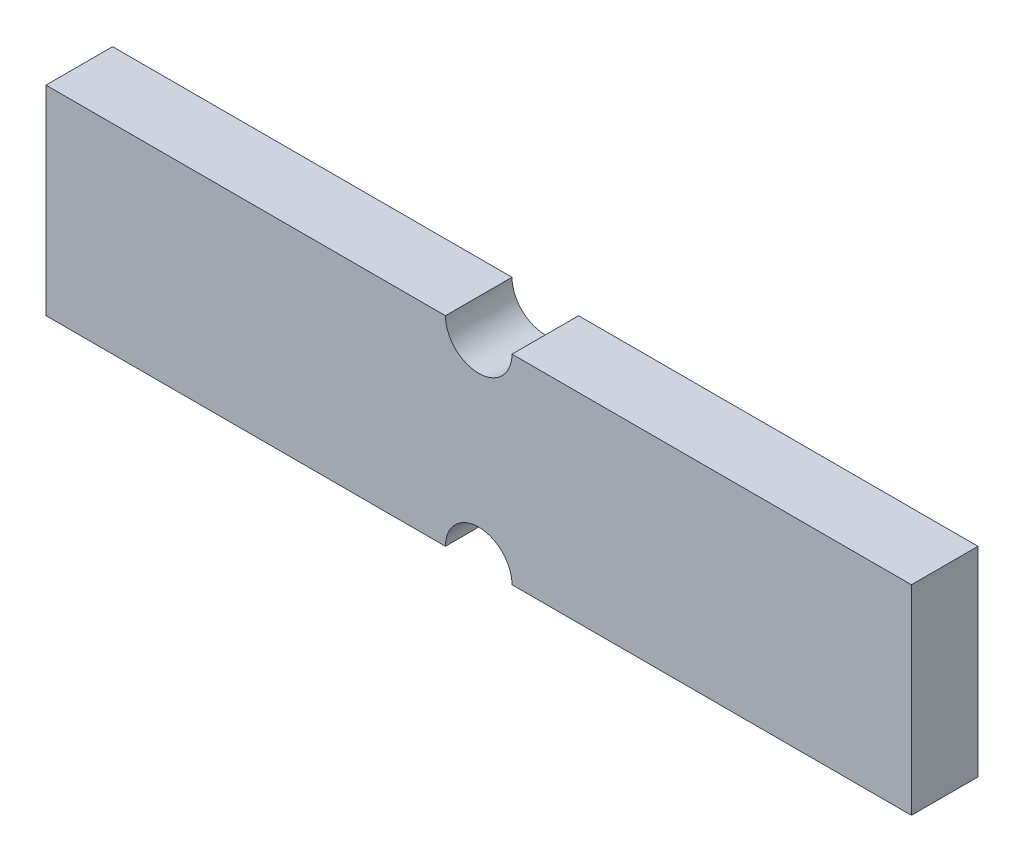
SolidWorks part; units mm, degrees
material "AISI 1020"
ref_plane "Front Plane" through (0, 0, 0) normal (0, 0, 1) x (1, 0, 0)
ref_plane "Top Plane" through (0, 0, 0) normal (0, 1, 0) x (1, 0, 0)
ref_plane "Right Plane" through (0, 0, 0) normal (1, 0, 0) x (0, 0, -1)
sketch "Sketch1" plane through (0, 0, 0) normal (0, 0, 1) x (1, 0, 0)
  line L0 (82.55, 74.4922) -> (82.55, -31.3198) construction
  line L1 (0, 0) -> (76.2, 0)
  line L2 (0, 0) -> (0, 38.1)
  line L3 (0, 38.1) -> (76.2, 38.1)
  line L4 (165.1, 0) -> (165.1, 38.1)
  line L5 (88.9, 38.1) -> (165.1, 38.1)
  line L6 (88.9, 0) -> (165.1, 0)
  arc A0 (88.9, 0) -> (76.2, 0) centre (82.55, 0) ccw
  arc A1 (76.2, 38.1) -> (88.9, 38.1) centre (82.55, 38.1) ccw
  dimension "D3" = 82.55
  dimension "D4" = 6.35
  dimension "D5" = 6.35
  dimension "D1" = 165.1
  dimension "D2" = 38.1
  dimension "D6" = 38.1
extrude "Extrude1" add sketch "Sketch1" along normal blind 12.7
ref_axis "Axis1" through (82.55, 38.1, 12.7) along (0, 0, -1)
fillet "Fillet1" [suppressed] radius 2.54
